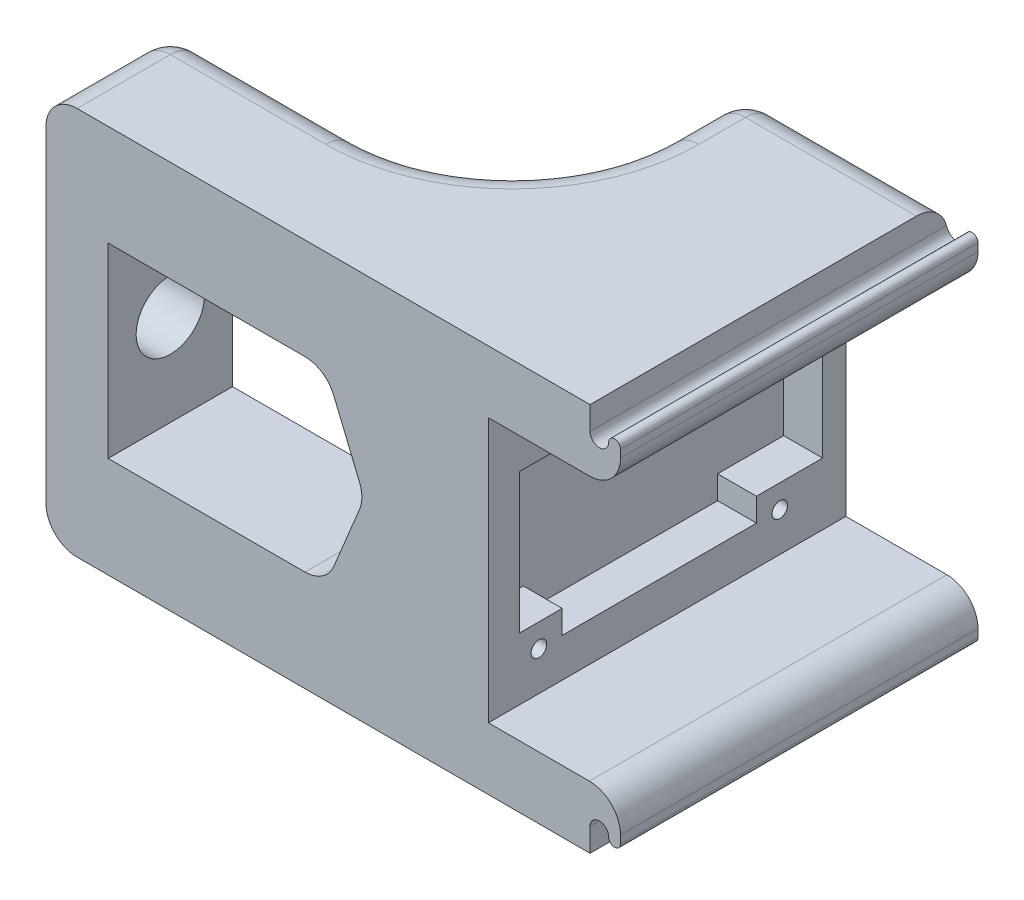
SolidWorks part; units mm, degrees
ref_plane "Přední rovina" through (0, 0, 0) normal (0, 0, 1) x (1, 0, 0)
ref_plane "Horní rovina" through (0, 0, 0) normal (0, 1, 0) x (1, 0, 0)
ref_plane "Pravá rovina" through (0, 0, 0) normal (1, 0, 0) x (0, 0, -1)
sketch "Skica1" plane through (0, 0, 0) normal (0, 0, 1) x (1, 0, 0)
  line L0 (0, 0) -> (0, 25)
  line L1 (0, 25) -> (35, 25)
  line L2 (35, 25) -> (35, 0)
  line L3 (35, 0) -> (0, 0)
  line L4 (4, 18.5) -> (4, 6.5)
  line L5 (4, 6.5) -> (18, 6.5)
  line L6 (18, 6.5) -> (20.4853, 12.5)
  line L7 (20.4853, 12.5) -> (18, 18.5)
  line L8 (18, 18.5) -> (4, 18.5)
  point P7 (4, 12.5)
  point P11 (0, 12.5)
  dimension "D1" = 25
  dimension "D2" = 12
  dimension "D3" = 4
  dimension "D4" = 14
  dimension "D5" = 14
  dimension "D6" = 135
  dimension "D7" = 35
extrude "Přidat vysunutím1" add sketch "Skica1" along normal blind 8
sketch "Skica2" plane through (0, 0, 0) normal (-1, 0, 0) x (0, 0, 1)
  line L0 (8, 25) -> (0, 25) construction
  line L1 (0, 25) -> (0, 0) construction
  circle A0 centre (4, 12.5) radius 2.2
  point P5 (4, 25)
  point P9 (0, 12.5)
  dimension "D1" = 4.4
extrude "Odebrat vysunutím1" cut sketch "Skica2" against normal blind 8
sketch "Skica3" plane through (0, 0, 0) normal (0, 0, -1) x (-1, 0, 0)
  line L0 (0, 0) -> (-35, 0) construction
  line L1 (-35, 25) -> (-22, 25)
  line L2 (-35, 25) -> (-35, 0)
  line L3 (-35, 0) -> (-22, 0)
  line L4 (-22, 25) -> (-22, 0)
  line L5 (-4, 18.5) -> (-4, 6.5) construction
  dimension "D1" = 18
extrude "Přidat vysunutím3" add sketch "Skica3" along normal blind 15
fillet "Zaoblit3" radius 10 1 edges at (22, 12.5, 0)
fillet "Zaoblit5" radius 2 1 edges at (0, 12.5, 0)
fillet "Zaoblit6" radius 2 5 edges at (0, 0, 5) (0.5858, 0, 0.5858) (7, 0, 0) (19.0711, 0, -2.9289) (22, 0, -12.5)
fillet "Zaoblit7" radius 2 5 edges at (0, 25, 5) (0.5858, 25, 0.5858) (7, 25, 0) (19.0711, 25, -2.9289) (22, 25, -12.5)
sketch "Skica6" plane through (0, 0, -15) normal (0, 0, -1) x (-1, 0, 0)
  line L0 (-35, 23.5) -> (-35, 1.5)
  line L1 (-35, 25) -> (-35, 0) construction
  line L2 (-36.96, 23.5) -> (-36.96, 1.5)
  arc A0 (-35, 23.5) -> (-36.2, 23.5) centre (-35.6, 23.5) cw
  arc A1 (-36.2, 23.5) -> (-36.96, 23.5) centre (-36.58, 23.5) ccw
  arc A2 (-35, 1.5) -> (-36.2, 1.5) centre (-35.6, 1.5) ccw
  arc A3 (-36.2, 1.5) -> (-36.96, 1.5) centre (-36.58, 1.5) cw
  dimension "D1" = 1.5
  dimension "D3" = 0.6
  dimension "D4" = 0.38
  dimension "D5" = 0.6
  dimension "D6" = 0.38
  dimension "D2" = 1.5
extrude "Přidat vysunutím6" add sketch "Skica6" against normal blind 23
fillet "Zaoblit12" radius 2 5 edges at (29.5, 0, -15) (22.5858, 0.5858, -15) (29.5, 25, -15) (22.5858, 24.4142, -15) (22, 12.5, -15)
fillet "Zaoblit13" radius 2 1 edges at (20.4853, 12.5, 1.6458)
fillet "Zaoblit14" radius 2 1 edges at (18, 18.5, 3)
fillet "Zaoblit15" radius 2 1 edges at (18, 6.5, 3)
sketch "Skica7" plane through (36.96, 0, 0) normal (1, 0, 0) x (0, 0, -1)
  line L0 (-8, 23.5) -> (-8, 1.5) construction
  line L1 (-8, 21) -> (15, 21)
  line L2 (-8, 21) -> (-8, 4)
  line L3 (-8, 4) -> (15, 4)
  line L4 (15, 21) -> (15, 4)
  line L5 (-8, 23.5) -> (15, 23.5) construction
  dimension "D1" = 23
  dimension "D2" = 0
  dimension "D3" = 17
  dimension "D4" = 2.5
extrude "Odebrat vysunutím4" cut sketch "Skica7" against normal blind 8.5
fillet "Zaoblit18" radius 2 1 edges at (36.96, 21, -3.5)
fillet "Zaoblit19" radius 2 1 edges at (36.96, 4, -3.5)
sketch "Skica8" plane through (28.46, 0, 0) normal (1, 0, 0) x (0, 0, -1)
  line L0 (-8, 21) -> (-8, 4) construction
  line L1 (-3, 17) -> (9, 17)
  line L2 (-3, 17) -> (-3, 8)
  line L3 (-3, 8) -> (9, 8)
  line L4 (9, 17) -> (9, 8)
  circle A0 centre (-4.75, 18.5) radius 0.5
  circle A1 centre (-4.75, 6.5) radius 0.5
  circle A2 centre (10.75, 18.5) radius 0.5
  circle A3 centre (10.75, 6.5) radius 0.5
  point P5 (0, 0)
  point P7 (-8, 12.5)
  point P8 (-3, 12.5)
  dimension "D4" = 1
  dimension "D5" = 1
  dimension "D6" = 1
  dimension "D7" = 1
  dimension "D1" = 9
  dimension "D2" = 12
  dimension "D3" = 5
  dimension "D8" = 1.5
  dimension "D9" = 1.75
  dimension "D10" = 1.75
  dimension "D11" = 1.5
extrude "Odebrat vysunutím5" cut sketch "Skica8" against normal blind 2
sketch "Skica9" plane through (28.46, 0, 0) normal (1, 0, 0) x (0, 0, -1)
  line L0 (9, 17) -> (-3, 17) construction
  line L1 (-6, 17) -> (13.5, 17)
  line L2 (-6, 17) -> (-6, 8)
  line L3 (-6, 8) -> (13.5, 8)
  line L4 (13.5, 17) -> (13.5, 8)
  line L5 (-3.25, 17) -> (9.25, 17)
  line L6 (-3.25, 17) -> (-3.25, 18.5)
  line L7 (-3.25, 18.5) -> (9.25, 18.5)
  line L8 (9.25, 17) -> (9.25, 18.5)
  line L9 (-3.25, 8) -> (9.25, 8)
  line L10 (-3.25, 8) -> (-3.25, 6.5)
  line L11 (-3.25, 6.5) -> (9.25, 6.5)
  line L12 (9.25, 8) -> (9.25, 6.5)
  line L13 (-3, 8) -> (9, 8) construction
  line L14 (-3, 17) -> (-3, 8) construction
  line L15 (9, 8) -> (9, 17) construction
  circle A0 centre (-4.75, 18.5) radius 0.5 construction
  circle A1 centre (10.75, 18.5) radius 0.5 construction
  circle A2 centre (-4.75, 6.5) radius 0.5 construction
  circle A3 centre (10.75, 6.5) radius 0.5 construction
  line M15 (-3, 8) -> (-3, 17)
  line M16 (-3, 17) -> (9, 17)
  line M17 (9, 17) -> (9, 8)
  line M18 (9, 8) -> (-3, 8)
  dimension "D6" = 1.5
  dimension "D7" = 1.5
  dimension "D1" = 3
  dimension "D2" = 4.5
  dimension "D3" = 1.5
  dimension "D4" = 1.5
  dimension "D5" = 1.5
  dimension "D8" = 1.5
extrude "Odebrat vysunutím6" cut sketch "Skica9" against normal blind 2.5 contours L2 L3 L1 M15 | L1 L8 L7 L6 M16 | L4 L1 L3 M17 | M15 M18 M17 M16 | L12 L3 L10 L11 M18 region at (28.46, 12.5, 4.5) region at (28.46, 17.75, -3) region at (28.46, 12.5, -3) region at (28.46, 7.25, -3) region at (28.46, 12.5, -11.25)
